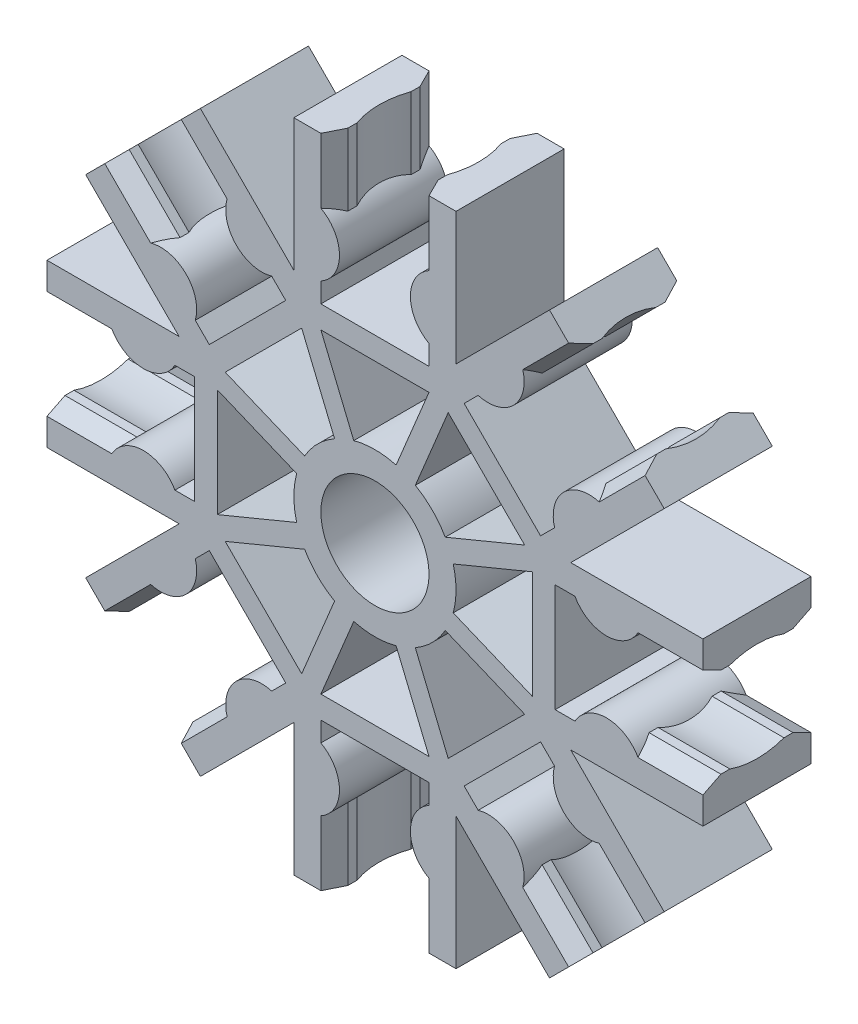
SolidWorks part; units mm, degrees
ref_plane "前视基准面" through (0, 0, 0) normal (0, 0, 1) x (1, 0, 0)
ref_plane "上视基准面" through (0, 0, 0) normal (0, 1, 0) x (1, 0, 0)
ref_plane "右视基准面" through (0, 0, 0) normal (1, 0, 0) x (0, 0, -1)
sketch "草图1" plane through (0, 0, 0) normal (0, 0, 1) x (1, 0, 0)
  line L0 (-4.5, 0) -> (-4.5, -18.2)
  line L1 (4.5, 0) -> (4.5, -18.2)
  line L2 (-4.5, -18.2) -> (-3, -18.2)
  line L3 (-3, -18.2) -> (-3, -14.6)
  line L4 (4.5, -18.2) -> (3, -18.2)
  line L5 (3, -18.2) -> (3, -14.6)
  line L6 (-3, -11.1) -> (-3, -10)
  line L7 (-3, -10) -> (3, -10)
  line L8 (3, -10) -> (3, -11.1)
  arc A0 (4.5, 0) -> (-4.5, 0) centre (0, 0) ccw
  arc A1 (-3, -11.1) -> (-3, -14.6) centre (-3.9682, -12.85) cw
  arc A2 (3, -11.1) -> (3, -14.6) centre (3.9682, -12.85) ccw
  point P1 (0, 4.5)
  dimension "D1" = 9
  dimension "D10" = 14.5
  dimension "D11" = 2
  dimension "D12" = 2
  dimension "D2" = 18.2
  dimension "D3" = 18.2
  dimension "D4" = 1.5
  dimension "D5" = 1.5
  dimension "D6" = 1.1
  dimension "D7" = 1.1
  dimension "D8" = 3.5
  dimension "D9" = 3.5
extrude "凸台-拉伸1" add sketch "草图1" along normal blind 6
sketch "草图3" plane through (0, -18.2, 0) normal (0, -1, 0) x (1, 0, 0)
  line L0 (-3, 6) -> (-3, 0)
  line L1 (-3, 0) -> (-2.5, 1)
  line L2 (-2.5, 1) -> (-2.5, 1.5)
  line L3 (-3, 6) -> (-2.5, 5)
  line L4 (-2.5, 5) -> (-2.5, 4.5)
  line L5 (0, 0) -> (0, 6.4845) construction
  line L6 (3, 0) -> (2.5, 1)
  line L7 (2.5, 1) -> (2.5, 1.5)
  line L8 (2.5, 5) -> (2.5, 4.5)
  line L9 (3, 6) -> (2.5, 5)
  line L10 (3, 6) -> (3, 0)
  arc A0 (-2.5, 1.5) -> (-2.5, 4.5) centre (1.7426, 3) cw
  arc A1 (2.5, 1.5) -> (2.5, 4.5) centre (-1.7426, 3) ccw
  dimension "D7" = 4.5
  dimension "D1" = 0.5
  dimension "D2" = 0.5
  dimension "D3" = 0.5
  dimension "D4" = 0.5
  dimension "D5" = 1.5
  dimension "D6" = 1.5
extrude "凸台-拉伸2" add sketch "草图3" against normal up to next
ref_axis "Axis" through (0, 0, 0) along (0, 0, 1)
pattern_circular "阵列(圆周)1" count 8 over 360 about axis through (0, 0, 0) along (0, 0, 1) of "凸台-拉伸1", "凸台-拉伸2"
sketch "草图4" plane through (0, 0, 0) normal (0, 0, -1) x (-1, 0, 0)
  line L0 (0, 0) -> (-4.5, -10.864) construction
  line L1 (0, 0) -> (4.5, -10.864) construction
  line L2 (0, 0) -> (0, -10) construction
  line L3 (3, -10) -> (-3, -10) construction
  line L4 (-3, -8.75) -> (3, -8.75)
  line L5 (-3, -8.75) -> (-1.1749, -4.3439)
  line L6 (3, -8.75) -> (1.1749, -4.3439)
  line L7 (-8.3085, -4.0659) -> (-3.9024, -2.2408)
  line L8 (-8.3085, -4.0659) -> (-4.0659, -8.3085)
  line L9 (-4.0659, -8.3085) -> (-2.2408, -3.9024)
  line L10 (-8.75, 3) -> (-4.3439, 1.1749)
  line L11 (-8.75, 3) -> (-8.75, -3)
  line L12 (-8.75, -3) -> (-4.3439, -1.1749)
  line L13 (-4.0659, 8.3085) -> (-2.2408, 3.9024)
  line L14 (-4.0659, 8.3085) -> (-8.3085, 4.0659)
  line L15 (-8.3085, 4.0659) -> (-3.9024, 2.2408)
  line L16 (3, 8.75) -> (1.1749, 4.3439)
  line L17 (3, 8.75) -> (-3, 8.75)
  line L18 (-3, 8.75) -> (-1.1749, 4.3439)
  line L19 (8.3085, 4.0659) -> (3.9024, 2.2408)
  line L20 (8.3085, 4.0659) -> (4.0659, 8.3085)
  line L21 (4.0659, 8.3085) -> (2.2408, 3.9024)
  line L22 (8.75, -3) -> (4.3439, -1.1749)
  line L23 (8.75, -3) -> (8.75, 3)
  line L24 (8.75, 3) -> (4.3439, 1.1749)
  line L25 (4.0659, -8.3085) -> (2.2408, -3.9024)
  line L26 (4.0659, -8.3085) -> (8.3085, -4.0659)
  line L27 (8.3085, -4.0659) -> (3.9024, -2.2408)
  circle A0 centre (0, 0) radius 3
  arc A1 (-2.2408, 3.9024) -> (-3.9024, 2.2408) centre (0, 0) ccw
  arc A2 (1.1749, 4.3439) -> (-1.1749, 4.3439) centre (0, 0) ccw
  arc A3 (3.9024, 2.2408) -> (2.2408, 3.9024) centre (0, 0) ccw
  arc A4 (4.3439, -1.1749) -> (4.3439, 1.1749) centre (0, 0) ccw
  arc A5 (2.2408, -3.9024) -> (3.9024, -2.2408) centre (0, 0) ccw
  arc A6 (-1.1749, -4.3439) -> (1.1749, -4.3439) centre (0, 0) ccw
  arc A7 (-3.9024, -2.2408) -> (-2.2408, -3.9024) centre (0, 0) ccw
  arc A8 (-4.3439, 1.1749) -> (-4.3439, -1.1749) centre (0, 0) ccw
  point P11 (0, -8.75)
  point P47 (0, 0)
  dimension "D3" = 9
  dimension "D4" = 6
  dimension "D1" = 6
  dimension "D2" = 1.25
  dimension "D5" = 8
extrude "切除-拉伸1" cut sketch "草图4" against normal through all
